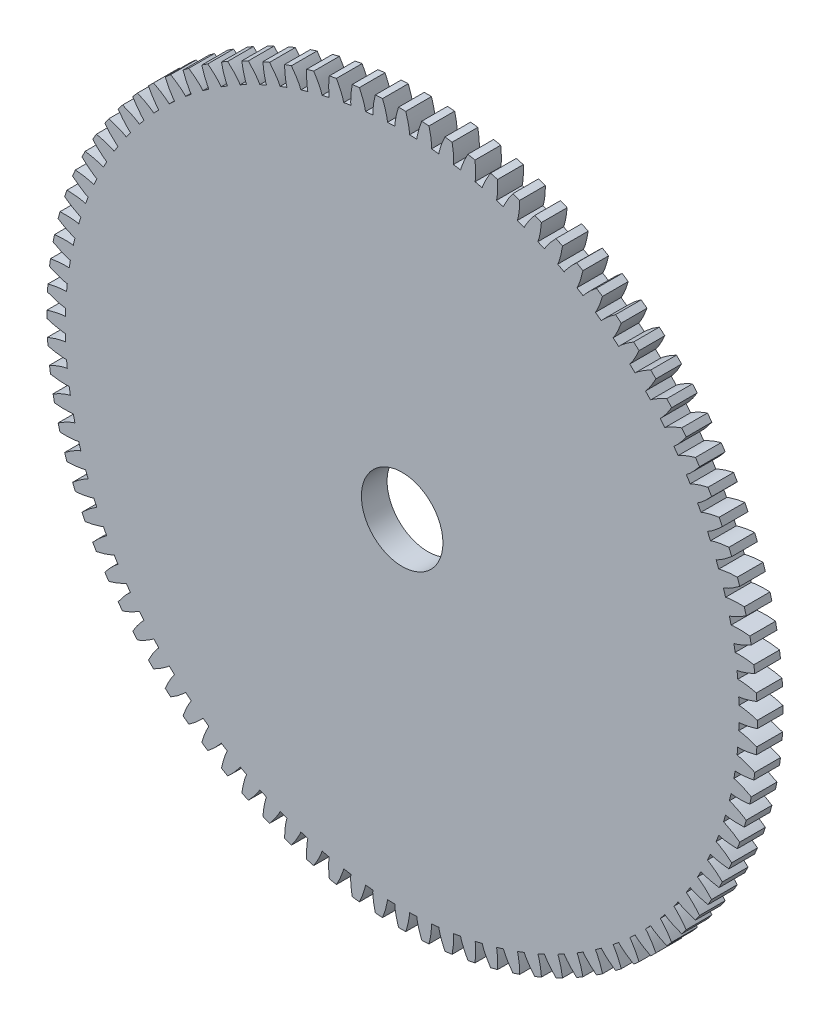
SolidWorks part; units mm, degrees
material "Brass"
ref_plane "Front Plane" through (0, 0, 0) normal (0, 0, 1) x (1, 0, 0)
ref_plane "Top Plane" through (0, 0, 0) normal (0, 1, 0) x (1, 0, 0)
ref_plane "Right Plane" through (0, 0, 0) normal (1, 0, 0) x (0, 0, -1)
sketch "Sketch1" plane through (0, 0, 0) normal (0, 0, 1) x (1, 0, 0)
  circle A0 centre (0, 0) radius 41.4867
  dimension "D1" = 82.9733
extrude "Boss-Extrude1" add sketch "Sketch1" along normal blind 3
sketch "Sketch2" plane through (0, 0, 0) normal (0, 0, 1) x (1, 0, 0)
  spline S0 degree 4 poles (39.3361, 0.8619) (39.3452, 0.862) (39.3625, 0.8619) (39.3906, 0.8613) (39.4298, 0.8597) (39.4764, 0.8572) (39.5312, 0.8534) (39.5916, 0.8482) (39.6575, 0.8417) (39.7232, 0.8342) (39.789, 0.826) (39.8545, 0.817) (39.9341, 0.8053) (40.0296, 0.7901) (40.1416, 0.7705) (40.2689, 0.7461) (40.3991, 0.7191) (40.5276, 0.6906) (40.6577, 0.6596) (40.784, 0.6281) (40.9157, 0.5932) (41.0374, 0.5599) (41.1744, 0.52) (41.285, 0.4872) (41.4317, 0.4412) (41.5185, 0.4132) (41.6203, 0.3795) (41.6656, 0.3641) (41.6936, 0.3546) knots 0 0 0 0 0 0.015084 0.028532 0.04661 0.064855 0.092111 0.119476 0.146842 0.174209 0.201575 0.228941 0.256307 0.307035 0.361767 0.4165 0.471232 0.525964 0.580697 0.635429 0.690161 0.744894 0.799626 0.854358 0.909091 0.954545 1 1 1 1 1 construction
  spline S1 degree 4 poles (39.3361, 0.8619) (39.3452, 0.862) (39.3625, 0.8619) (39.3906, 0.8613) (39.4298, 0.8597) (39.4764, 0.8572) (39.5312, 0.8534) (39.5916, 0.8482) (39.6575, 0.8417) (39.7232, 0.8342) (39.789, 0.826) (39.8545, 0.817) (39.9341, 0.8053) (40.0296, 0.7901) (40.1416, 0.7705) (40.2689, 0.7461) (40.3991, 0.7191) (40.5276, 0.6906) (40.6577, 0.6596) (40.784, 0.6281) (40.9157, 0.5932) (41.0374, 0.5599) (41.1744, 0.52) (41.285, 0.4872) (41.3999, 0.4511) (41.4559, 0.4333) (41.4845, 0.424) knots 0 0 0 0 0 0.015084 0.028532 0.04661 0.064855 0.092111 0.119476 0.146842 0.174209 0.201575 0.228941 0.256307 0.307035 0.361767 0.4165 0.471232 0.525964 0.580697 0.635429 0.690161 0.744894 0.799626 0.854358 0.909091 0.909091 0.909091 0.909091 0.909091
  spline S2 degree 4 poles (39.3082, 1.7127) (39.3173, 1.7131) (39.3346, 1.7144) (39.3626, 1.7168) (39.4017, 1.7209) (39.4479, 1.7265) (39.5024, 1.7339) (39.5624, 1.743) (39.6276, 1.7539) (39.6928, 1.7656) (39.7578, 1.7781) (39.8226, 1.7913) (39.9012, 1.8082) (39.9956, 1.8297) (40.1061, 1.8566) (40.2315, 1.8892) (40.3597, 1.9247) (40.486, 1.9615) (40.6138, 2.0009) (40.7378, 2.0406) (40.8668, 2.084) (40.9861, 2.1253) (41.1202, 2.174) (41.2285, 2.214) (41.3718, 2.2696) (41.4566, 2.3031) (41.556, 2.3434) (41.6002, 2.3618) (41.6275, 2.373) knots 0 0 0 0 0 0.015084 0.028532 0.04661 0.064855 0.092111 0.119476 0.146842 0.174209 0.201575 0.228941 0.256307 0.307035 0.361767 0.4165 0.471232 0.525964 0.580697 0.635429 0.690161 0.744894 0.799626 0.854358 0.909091 0.954545 1 1 1 1 1 construction
  spline S3 degree 4 poles (39.3082, 1.7127) (39.3173, 1.7131) (39.3346, 1.7144) (39.3626, 1.7168) (39.4017, 1.7209) (39.4479, 1.7265) (39.5024, 1.7339) (39.5624, 1.743) (39.6276, 1.7539) (39.6928, 1.7656) (39.7578, 1.7781) (39.8226, 1.7913) (39.9012, 1.8082) (39.9956, 1.8297) (40.1061, 1.8566) (40.2315, 1.8892) (40.3597, 1.9247) (40.486, 1.9615) (40.6138, 2.0009) (40.7378, 2.0406) (40.8668, 2.084) (40.9861, 2.1253) (41.1202, 2.174) (41.2285, 2.214) (41.3408, 2.2575) (41.3954, 2.279) (41.4234, 2.2901) knots 0 0 0 0 0 0.015084 0.028532 0.04661 0.064855 0.092111 0.119476 0.146842 0.174209 0.201575 0.228941 0.256307 0.307035 0.361767 0.4165 0.471232 0.525964 0.580697 0.635429 0.690161 0.744894 0.799626 0.854358 0.909091 0.909091 0.909091 0.909091 0.909091
  spline S4 degree 1 poles (39.3082, 1.7127) (39.3361, 0.8619) knots 0 0 1 1 construction
  spline S5 degree 1 poles (39.3082, 1.7127) (39.3361, 0.8619) knots 0 0 1 1
  spline S6 degree 1 poles (41.4845, 0.424) (59.9969, 0.6133) knots 0 0 1 1 construction
  spline S7 degree 1 poles (41.4845, 0.424) (59.9969, 0.6133) knots 0 0 1 1
  spline S8 degree 4 poles (59.999, 0.3414) (59.9989, 0.3608) (59.9987, 0.3983) (59.9984, 0.449) (59.9972, 0.5864) (59.9966, 0.6465) (59.9945, 0.8237) (59.9929, 0.9242) (59.9906, 1.0696) (59.9883, 1.188) (59.9855, 1.3227) (59.9826, 1.4476) (59.9793, 1.5783) (59.9758, 1.7056) (59.972, 1.8348) (59.9679, 1.9631) (59.9636, 2.0915) (59.9589, 2.2206) (59.9541, 2.3479) (59.9488, 2.4785) (59.9436, 2.6033) (59.9375, 2.7379) (59.9321, 2.8562) (59.9249, 3.0015) (59.9199, 3.1019) (59.9104, 3.2789) (59.9071, 3.3389) (59.8993, 3.4761) (59.8963, 3.5267) (59.8941, 3.5641) (59.8929, 3.5834) knots 0 0 0 0 0 0.020959 0.041918 0.083333 0.123016 0.162698 0.202381 0.242063 0.281746 0.321429 0.361111 0.400794 0.440476 0.480159 0.519841 0.559524 0.599206 0.638889 0.678571 0.718254 0.757937 0.797619 0.837302 0.876984 0.916667 0.958082 0.979041 1 1 1 1 1 construction
  spline S9 degree 4 poles (59.9969, 0.6133) (59.9966, 0.64) (59.996, 0.6922) (59.9945, 0.8237) (59.9929, 0.9242) (59.9906, 1.0696) (59.9883, 1.188) (59.9855, 1.3227) (59.9826, 1.4476) (59.9793, 1.5783) (59.9758, 1.7056) (59.972, 1.8348) (59.9679, 1.9631) (59.9636, 2.0915) (59.9589, 2.2206) (59.9541, 2.3479) (59.9488, 2.4785) (59.9436, 2.6033) (59.9375, 2.7379) (59.9321, 2.8562) (59.9249, 3.0015) (59.9199, 3.1019) (59.9128, 3.2332) (59.91, 3.2853) (59.9085, 3.312) knots 0.083333 0.083333 0.083333 0.083333 0.083333 0.123016 0.162698 0.202381 0.242063 0.281746 0.321429 0.361111 0.400794 0.440476 0.480159 0.519841 0.559524 0.599206 0.638889 0.678571 0.718254 0.757937 0.797619 0.837302 0.876984 0.916667 0.916667 0.916667 0.916667 0.916667
  spline S10 degree 1 poles (59.9085, 3.312) (41.4234, 2.2901) knots 0 0 1 1 construction
  spline S11 degree 1 poles (59.9085, 3.312) (41.4234, 2.2901) knots 0 0 1 1
extrude "Cut-Extrude2" cut sketch "Sketch2" against normal blind 4 and the other way blind 4
ref_axis "Axis1" through (0, 0, -0.15) along (0, 0, 1)
pattern_circular "CirPattern1" count 96 over 360 about axis through (0, 0, -0.15) along (0, 0, 1) of "Cut-Extrude2"
sketch "Sketch3" plane through (0, 0, 0) normal (0, 0, 1) x (1, 0, 0)
  circle A0 centre (0, 0) radius 4.7625
  dimension "D1" = 9.525
extrude "Cut-Extrude4" cut sketch "Sketch3" against normal blind 5 and the other way blind 5
